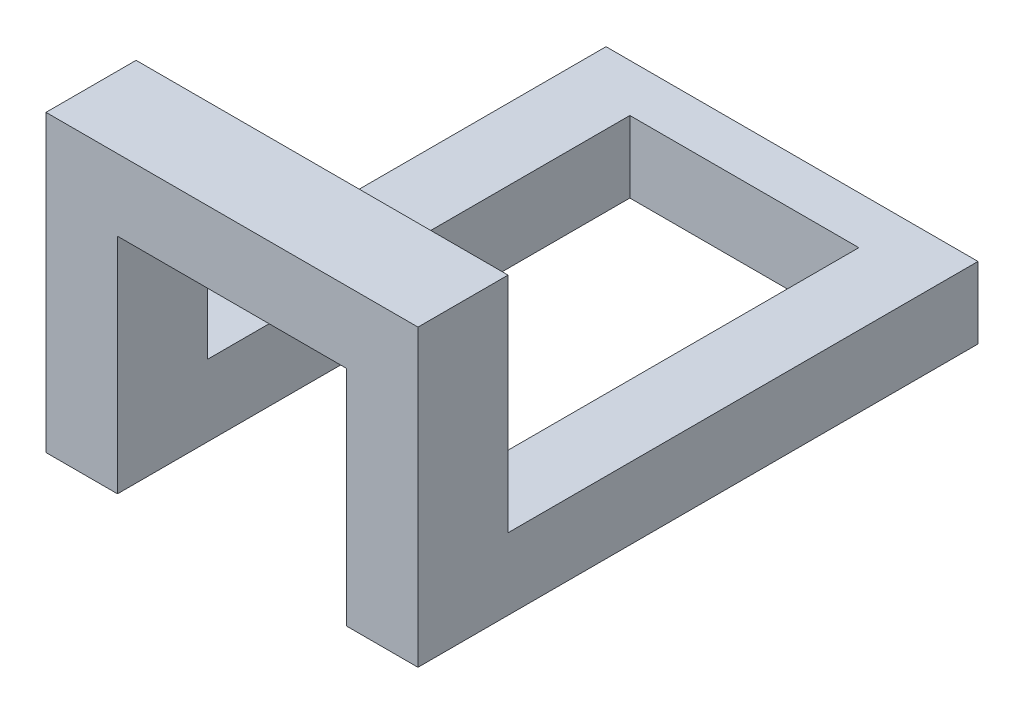
SolidWorks part; units mm, degrees
ref_plane "Front Plane" through (0, 0, 0) normal (0, 0, 1) x (1, 0, 0)
ref_plane "Top Plane" through (0, 0, 0) normal (0, 1, 0) x (1, 0, 0)
ref_plane "Right Plane" through (0, 0, 0) normal (1, 0, 0) x (0, 0, -1)
sketch "Sketch1" plane through (0, 0, 0) normal (0, 1, 0) x (1, 0, 0)
  line L12 (44.2903, 10.1471) -> (44.2903, 14.9471)
  line L13 (44.2903, 10.1471) -> (24.4703, 10.1471)
  line L16 (24.4703, 10.1471) -> (24.4703, 14.9471)
  line L17 (24.4703, 14.9471) -> (44.2903, 14.9471)
  line L18 (39.6303, 14.9471) -> (35.9423, 14.9471) construction
  line L19 (34.9303, 10.1471) -> (39.6303, 10.1471) construction
  line L20 (40.4803, 10.9971) -> (40.4803, 15.7971) construction
  line L21 (28.2803, 15.7971) -> (28.2803, 10.9971) construction
  dimension "D1" = 3.81
  dimension "D2" = 3.81
extrude "Boss-Extrude1" add sketch "Sketch1" along normal blind 3.81 contours L17 L12 L13 L16
sketch "Sketch2" plane through (0, 0, 0) normal (0, -1, 0) x (1, 0, 0)
  line L0 (24.4703, -14.9471) -> (44.2903, -14.9471) construction
  line L1 (24.4703, -10.1471) -> (28.2803, -10.1471)
  line L2 (24.4703, -10.1471) -> (24.4703, -14.9471)
  line L3 (24.4703, -14.9471) -> (28.2803, -14.9471)
  line L4 (28.2803, -10.1471) -> (28.2803, -14.9471)
  line L5 (44.2903, -10.1471) -> (24.4703, -10.1471) construction
  line L6 (44.2903, -14.9471) -> (40.4803, -14.9471)
  line L7 (44.2903, -14.9471) -> (44.2903, -10.1471)
  line L8 (44.2903, -10.1471) -> (40.4803, -10.1471)
  line L9 (40.4803, -14.9471) -> (40.4803, -10.1471)
  dimension "D1" = 3.81
  dimension "D2" = 3.81
extrude "Boss-Extrude2" add sketch "Sketch2" along normal up to surface (11.89 mm away)
sketch "Sketch3" plane through (0, 0, -14.9471) normal (0, 0, -1) x (-1, 0, 0)
  line L0 (-40.4803, -11.89) -> (-40.4803, 0) construction
  line L1 (-44.2903, -11.89) -> (-40.4803, -11.89)
  line L2 (-44.2903, -11.89) -> (-44.2903, -8.08)
  line L3 (-44.2903, -8.08) -> (-40.4803, -8.08)
  line L4 (-40.4803, -11.89) -> (-40.4803, -8.08)
  line L11 (-24.4703, 3.81) -> (-24.4703, -11.89) construction
  line L12 (-28.2803, -11.89) -> (-24.4703, -11.89)
  line L13 (-28.2803, -11.89) -> (-28.2803, -8.08)
  line L14 (-28.2803, -8.08) -> (-24.4703, -8.08)
  line L15 (-24.4703, -11.89) -> (-24.4703, -8.08)
  dimension "D1" = 3.81
  dimension "D2" = 3.81
extrude "Boss-Extrude3" add sketch "Sketch3" along normal up to surface (22.5 mm away)
sketch "Sketch4" plane through (0, 0, -37.4471) normal (0, 0, -1) x (-1, 0, 0)
  line L1 (-44.2903, -8.08) -> (-24.4703, -8.08)
  line L2 (-44.2903, -8.08) -> (-44.2903, -11.89)
  line L3 (-44.2903, -11.89) -> (-24.4703, -11.89)
  line L4 (-24.4703, -8.08) -> (-24.4703, -11.89)
extrude "Boss-Extrude4" add sketch "Sketch4" along normal blind 2.54
sketch "Sketch5" plane through (0, 0, -39.9871) normal (0, 0, -1) x (-1, 0, 0)
  circle A0 centre (-37.896, -9.9125) radius 1.2621
